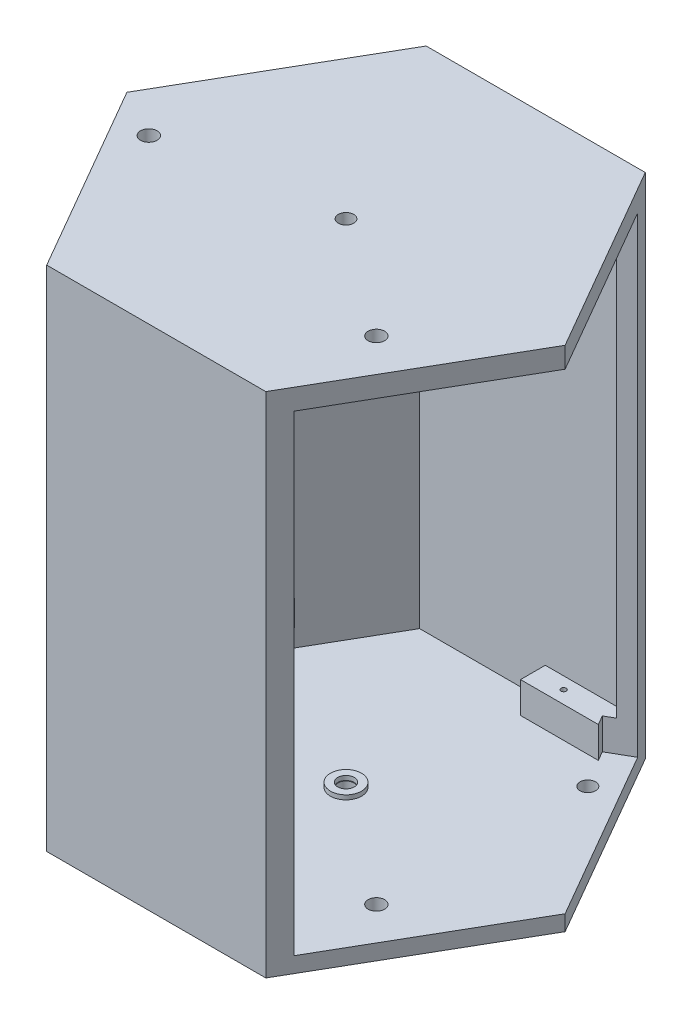
SolidWorks part; units mm, degrees
note: The reader was unsure of these and kept them because the rebuilt part matched: shared geometry of "Sketch1<3>", "Sketch5<2>".
ref_plane "Front Plane" through (0, 0, 0) normal (0, 0, 1) x (1, 0, 0)
ref_plane "Top Plane" through (0, 0, 0) normal (0, 1, 0) x (1, 0, 0)
ref_plane "Right Plane" through (0, 0, 0) normal (1, 0, 0) x (0, 0, -1)
sketch "Sketch1" plane through (0, 0, 0) normal (0, 1, 0) x (1, 0, 0)
  line L6 (-40.5739, 73.8992) -> (-82.8536, 0.6687)
  line L7 (-75.9254, 0.6687) -> (-37.1098, -66.5618)
  line L8 (-37.1098, -66.5618) -> (40.5213, -66.5618)
  line L9 (40.5213, -66.5618) -> (79.3368, 0.6687)
  line L10 (79.3368, 0.6687) -> (40.5213, 67.8992)
  line L11 (40.5213, 67.8992) -> (-37.1098, 67.8992)
  line L12 (-37.1098, 67.8992) -> (-75.9254, 0.6687)
  line L13 (-82.8536, 0.6687) -> (-40.5739, -72.5618)
  line L14 (-40.5739, -72.5618) -> (43.9854, -72.5618)
  line L15 (43.9854, -72.5618) -> (86.265, 0.6687)
  line L16 (86.265, 0.6687) -> (43.9854, 73.8992)
  line L17 (43.9854, 73.8992) -> (-40.5739, 73.8992)
  circle A4 centre (1.7057, 0.6687) radius 2.9711
  circle A5 centre (1.7057, 0.6687) radius 67.2305 construction
  dimension "D2" = 6
extrude "Boss-Extrude2" add sketch "Sketch1" along normal blind 6
extrude "Boss-Extrude3" add sketch "Sketch1<3>" along normal blind 190 contours L16 L17 L6 L13 L14 L15 L12 L11 L10 L9 L8 L7
sketch "Sketch1<3>" plane through (0, 0, 0) normal (0, 1, 0) x (1, 0, 0) same geometry as "Sketch1"
sketch "Sketch3" plane through (0, 190, 0) normal (0, 1, 0) x (1, 0, 0)
  line L9 (86.265, 0.6687) -> (43.9854, 73.8992)
  line L10 (43.9854, -72.5618) -> (86.265, 0.6687)
  line L30 (-40.5739, -72.5618) -> (43.9854, -72.5618)
  line L31 (-82.8536, 0.6687) -> (-40.5739, -72.5618)
  line L32 (-40.5739, 73.8992) -> (-82.8536, 0.6687)
  line L33 (43.9854, 73.8992) -> (-40.5739, 73.8992)
  line L34 (86.265, 0.6687) -> (43.9854, 73.8992)
  line L35 (43.9854, -72.5618) -> (86.265, 0.6687)
  line L36 (-40.5739, -72.5618) -> (43.9854, -72.5618)
  line L37 (-82.8536, 0.6687) -> (-40.5739, -72.5618)
  line L38 (-40.5739, 73.8992) -> (-82.8536, 0.6687)
  line L39 (43.9854, 73.8992) -> (-40.5739, 73.8992)
  circle A1 centre (1.7057, 0.6687) radius 2.9711
  circle A2 centre (1.7057, 0.6687) radius 2.9711
  dimension "D1" = 0
  dimension "D3" = 0
extrude "Boss-Extrude5" add sketch "Sketch3" along normal blind 6
sketch "Sketch4" plane through (-62.4297, 0, -36.0438) normal (-0.866, 0, -0.5) x (-0.5, 0, 0.866)
  line L0 (40.2248, 26.3) -> (40.2248, 16.3) construction
  line L1 (-3.4948, 16.3) -> (-3.4948, 26.3) construction
  line L2 (-3.4948, 26.3) -> (40.2248, 26.3) construction
  line L3 (40.2248, 16.3) -> (-3.4948, 16.3) construction
  line L5 (40.2248, 26.3) -> (40.2248, 16.3)
  line L6 (-3.4948, 16.3) -> (-3.4948, 26.3)
  line L7 (-3.4948, 26.3) -> (40.2248, 26.3)
  line L8 (40.2248, 16.3) -> (-3.4948, 16.3)
  line L9 (9.0052, 26.3) -> (9.0052, 16.3)
  dimension "D1" = 12.5
extrude "Boss-Extrude6" add sketch "Sketch4" against normal blind 11 contours L9 L7 L6 L8
sketch "Sketch5" plane through (0, 0, 0) normal (0, -1, 0) x (1, 0, 0)
  line L9 (-37.1098, -67.8992) -> (40.5213, -67.8992) construction
  line L16 (40.5213, -67.8992) -> (11.391, -67.8992)
  line L17 (46.0435, -58.3345) -> (40.5213, -67.8992)
  line L18 (40.5213, -67.8992) -> (79.3368, -0.6687) construction
  line L19 (46.0435, -58.3345) -> (11.391, -58.3345)
  line L20 (11.391, -58.3345) -> (11.391, -67.8992)
  circle A0 centre (23.0913, -63.2739) radius 1
  circle A1 centre (37.5239, -36.9737) radius 1.25 construction
  point P0 (25.4923, -58.9525)
  dimension "D1" = 2
  dimension "D2" = 30
extrude "Boss-Extrude8" add sketch "Sketch5" against normal blind 18
extrude "Cut-Extrude2" cut sketch "Sketch5<2>" against normal blind 18 contours A0
sketch "Sketch5<2>" plane through (0, 0, 0) normal (0, -1, 0) x (1, 0, 0) same geometry as "Sketch5"
sketch "Sketch7" plane through (0, 196, 0) normal (0, 1, 0) x (1, 0, 0)
  circle A0 centre (1.7057, 0.6687) radius 6
  circle A1 centre (1.7057, 0.6687) radius 3.2 construction
  circle A2 centre (1.7057, 0.6687) radius 3.2
  dimension "D1" = 12
extrude "Boss-Extrude9" add sketch "Sketch7" against normal blind 7.7
sketch "Sketch8" plane through (0, 0, 0) normal (0, -1, 0) x (1, 0, 0)
  circle A0 centre (1.7057, -0.6687) radius 6
  circle A1 centre (1.7057, -0.6687) radius 3.2 construction
  circle A2 centre (1.7057, -0.6687) radius 3.2
  dimension "D1" = 12
extrude "Boss-Extrude10" add sketch "Sketch8" against normal blind 7.7
extrude "Cut-Extrude3" cut sketch "Sketch9" along normal blind 6
sketch "Sketch9" plane through (629.827, 1366.4966, -942.1455) normal (-0.866, 0, -0.5) x (0, -1, 0)
  line L1 (1178.4966, 1163.6831) -> (1360.4966, 1163.6831)
  line L2 (1178.4966, 1163.6831) -> (1178.4966, 1087.1238)
  line L3 (1178.4966, 1087.1238) -> (1360.4966, 1087.1238)
  line L13 (1360.4966, 1163.6831) -> (1360.4966, 1087.1238)
extrude "Cut-Extrude5" cut sketch "Sketch11" against normal blind 6
sketch "Sketch11" plane through (508.1842, 1366.4966, 1023.0387) normal (-0.866, 0, 0.5) x (0, 1, 0)
  line L0 (-1331.4966, 1182.0754) -> (-1360.4966, 1182.0754)
  line L3 (-1360.4966, 1157.0754) -> (-1331.4966, 1157.0754)
  line L4 (-1331.4966, 1182.0754) -> (-1331.4966, 1157.0754)
  line L6 (-1360.4966, 1182.0754) -> (-1360.4966, 1157.0754)
extrude "Cut-Extrude6" cut sketch "Sketch12" against normal blind 6
sketch "Sketch12" plane through (-287.0905, 1366.4966, 353.08) normal (-0.866, 0, -0.5) x (0, 1, 0)
  line L0 (-1360.4966, 433.4738) -> (-1360.4966, 408.4738)
  line L1 (-1360.4966, 408.4738) -> (-1331.4966, 408.4738)
  line L3 (-1360.4966, 433.4738) -> (-1331.4966, 433.4738)
  line L4 (-1331.4966, 408.4738) -> (-1331.4966, 433.4738)
extrude "Cut-Extrude7" cut sketch "Sketch13" against normal blind 6
sketch "Sketch13" plane through (690.7481, 0, 917.6353) normal (0, -1, 0) x (-1, 0, 0)
  circle A2 centre (754.9247, 908.0784) radius 3.2
  circle A3 centre (644.0155, 885.0087) radius 3.2
  circle A5 centre (642.6894, 965.287) radius 3
extrude "Cut-Extrude8" cut sketch "Sketch14" against normal through all
sketch "Sketch14" plane through (690.7481, 0, 917.6353) normal (0, -1, 0) x (-1, 0, 0)
  circle A2 centre (754.9247, 908.0784) radius 3.2
  circle A3 centre (644.0155, 885.0087) radius 3.2
  circle A5 centre (642.6894, 965.287) radius 3
extrude "Cut-Extrude9" cut sketch "Sketch15" against normal blind 11
sketch "Sketch15" plane through (690.7481, 16.3, 917.6353) normal (0, -1, 0) x (-1, 0, 0)
  circle A0 centre (747.4757, 946.5554) radius 1
extrude "Cut-Extrude11" cut sketch "Sketch17" against normal blind 170
sketch "Sketch17" plane through (690.7481, 198, 917.6353) normal (0, 1, 0) x (1, 0, 0)
  circle A2 centre (-754.9247, 908.0784) radius 3
extrude "Cut-Extrude13" cut sketch "Sketch19" along normal through all and the other way through all
sketch "Sketch19" plane through (690.7481, 18, 917.6353) normal (0, -1, 0) x (-1, 0, 0)
  circle A1 centre (644.0155, 885.0087) radius 3.2
  circle A3 centre (754.9247, 908.0784) radius 3.2
extrude "Cut-Extrude14" cut sketch "Sketch20" along normal blind 10
sketch "Sketch20" plane through (-165.4477, 1366.4966, -436.6479) normal (-0.866, 0, 0.5) x (0, -1, 0)
  line L1 (1178.4966, 503.4254) -> (1360.4966, 503.4254)
  line L2 (1178.4966, 503.4254) -> (1178.4966, 426.8661)
  line L3 (1178.4966, 426.8661) -> (1360.4966, 426.8661)
  line L4 (1360.4966, 503.4254) -> (1360.4966, 426.8661)
